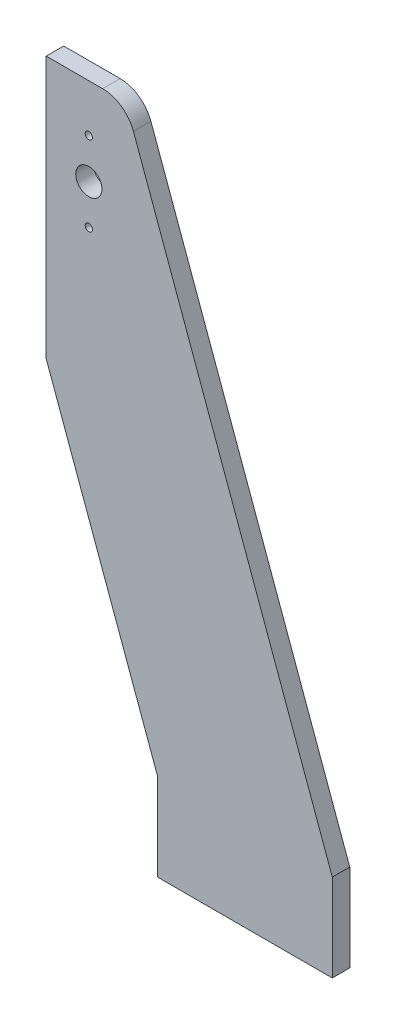
SolidWorks part; units mm, degrees
ref_plane "Alzado" through (0, 0, 0) normal (0, 0, 1) x (1, 0, 0)
ref_plane "Planta" through (0, 0, 0) normal (0, 1, 0) x (1, 0, 0)
ref_plane "Vista lateral" through (0, 0, 0) normal (1, 0, 0) x (0, 0, -1)
sketch "Croquis1" plane through (0, 0, 0) normal (0, 0, 1) x (1, 0, 0)
  line L0 (80, 0) -> (80, 40)
  line L1 (-50.9558, 300) -> (-25.1354, 300)
  line L2 (-50.9558, 300) -> (-50.9558, 180)
  line L3 (0, 0) -> (80, 0)
  line L4 (-11.04, 290.1303) -> (80, 40)
  line L9 (-50.9558, 180) -> (0, 40)
  line L11 (0, 40) -> (0, 0)
  arc A2 (-11.04, 290.1303) -> (-25.1354, 300) centre (-25.1354, 285) ccw
  point P6 (0, 0)
  point P9 (-50.9558, 300)
  point P11 (0, 0)
  dimension "D7" = 110
  dimension "D9" = 15
  dimension "D1" = 40
  dimension "D2" = 300
  dimension "D3" = 80
  dimension "D6" = 40
  dimension "D10" = 110
extrude "Saliente-Extruir1" add sketch "Croquis1" along normal blind 8
sketch "Croquis2" plane through (0, 0, 0) normal (0, 0, -1) x (-1, 0, 0)
  line L0 (25.1354, 300) -> (50.9558, 300) construction
  line L2 (50.9558, 300) -> (50.9558, 180) construction
  circle A0 centre (31.4558, 260) radius 6
  point P8 (50.9558, 229.009)
  dimension "D3" = 12
  dimension "D1" = 40
  dimension "D2" = 19.5
extrude "Cortar-Extruir1" cut sketch "Croquis2" against normal through all
hole_wizard "Perforador para roscar para macho de roscar para M44" positions "Croquis7" profile "Croquis8" hole size "M4" standard "DIN"
sketch "Croquis7" plane through (0, 0, 8) normal (0, 0, 1) x (1, 0, 0)
  line L0 (-31.4558, 278.25) -> (-31.4558, 241.75)
  circle A0 centre (-31.4558, 260) radius 6 construction
  point P1 (-31.4558, 278.25)
  point P2 (-31.4558, 241.75)
  dimension "D1" = 18.25
  dimension "D2" = 18.25
sketch "Croquis8" plane through (-31.4558, 278.25, 8) normal (1, 0, 0) x (0, -1, 0)
  line L0 (0, 0) -> (0, 7.9914)
  line L1 (0, 7.9914) -> (1.65, 7)
  line L2 (1.65, 7) -> (1.65, 0)
  line L5 (1.65, 0) -> (0, 0)
  line L10 (0, 7.9914) -> (-1.65, 7) construction
  line L11 (0, -6.35) -> (0, 107.95) construction
  dimension "Diámetro de taladro" = 3.3
  dimension "Profundidad de taladro" = 7
  dimension "Ángulo de perforador" = 118
